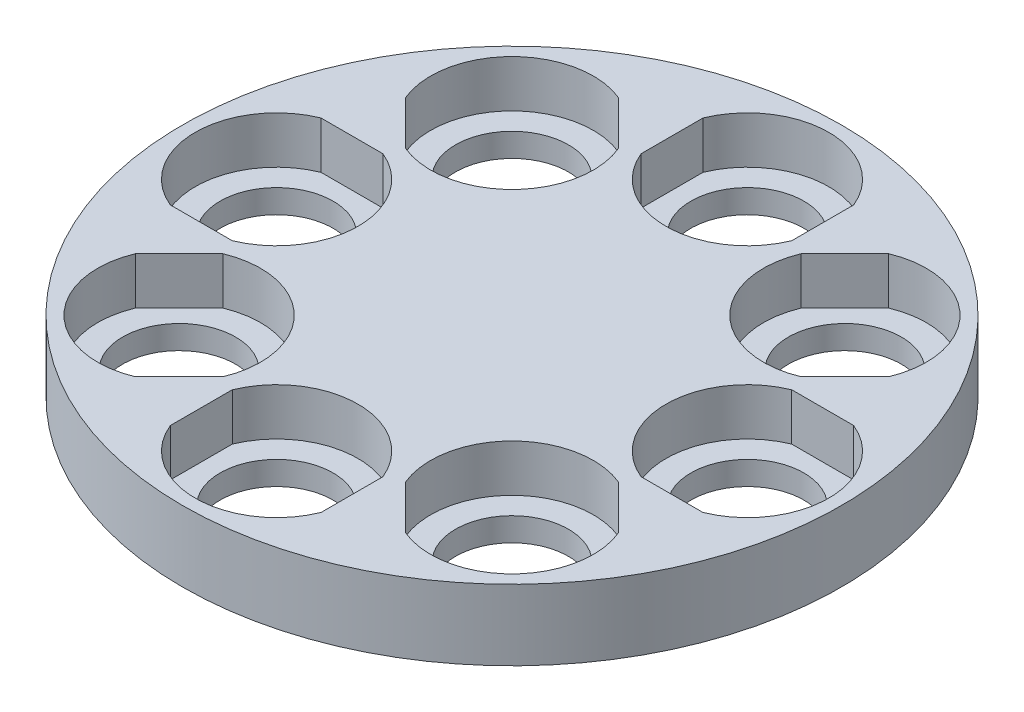
SolidWorks part; units mm, degrees
ref_plane "Front Plane" through (0, 0, 0) normal (0, 0, 1) x (1, 0, 0)
ref_plane "Top Plane" through (0, 0, 0) normal (0, 1, 0) x (1, 0, 0)
ref_plane "Right Plane" through (0, 0, 0) normal (1, 0, 0) x (0, 0, -1)
sketch "Sketch1" plane through (0, 0, 0) normal (0, 1, 0) x (1, 0, 0)
  line L0 (70, 0) -> (50, 0) construction
  circle A0 centre (0, 0) radius 70
  circle A1 centre (50, 0) radius 12
  circle A2 centre (35.3553, -35.3553) radius 12
  circle A3 centre (0, -50) radius 12
  circle A4 centre (-35.3553, -35.3553) radius 12
  circle A5 centre (-50, 0) radius 12
  circle A6 centre (-35.3553, 35.3553) radius 12
  circle A7 centre (0, 50) radius 12
  circle A8 centre (35.3553, 35.3553) radius 12
  point P23 (0, 0)
  dimension "D1" = 140
  dimension "D3" = 24
  dimension "D2" = 20
  dimension "D4" = 8
extrude "Boss-Extrude1" add sketch "Sketch1" along normal blind 25
sketch "Sketch2" plane through (0, 25, 0) normal (0, 1, 0) x (1, 0, 0)
  line L0 (50, 0) -> (50, 16) construction
  line L1 (50, 16) -> (43.4205, 16)
  line L2 (50, 16) -> (56.5795, 16)
  line L3 (32.7, 0) -> (67.3, 0) construction
  line L4 (50, -16) -> (56.5795, -16)
  line L5 (50, -16) -> (43.4205, -16)
  line L6 (46.669, -24.0416) -> (42.0166, -19.3892)
  line L7 (24.0416, -46.669) -> (19.3892, -42.0166)
  line L8 (24.0416, -46.669) -> (28.694, -51.3215)
  line L9 (46.669, -24.0416) -> (51.3215, -28.694)
  line L10 (16, -50) -> (16, -43.4205)
  line L11 (-16, -50) -> (-16, -43.4205)
  line L12 (-16, -50) -> (-16, -56.5795)
  line L13 (16, -50) -> (16, -56.5795)
  line L14 (-24.0416, -46.669) -> (-19.3892, -42.0166)
  line L15 (-46.669, -24.0416) -> (-42.0166, -19.3892)
  line L16 (-46.669, -24.0416) -> (-51.3215, -28.694)
  line L17 (-24.0416, -46.669) -> (-28.694, -51.3215)
  line L18 (-50, -16) -> (-43.4205, -16)
  line L19 (-50, 16) -> (-43.4205, 16)
  line L20 (-50, 16) -> (-56.5795, 16)
  line L21 (-50, -16) -> (-56.5795, -16)
  line L22 (-46.669, 24.0416) -> (-42.0166, 19.3892)
  line L23 (-24.0416, 46.669) -> (-19.3892, 42.0166)
  line L24 (-24.0416, 46.669) -> (-28.694, 51.3215)
  line L25 (-46.669, 24.0416) -> (-51.3215, 28.694)
  line L26 (-16, 50) -> (-16, 43.4205)
  line L27 (16, 50) -> (16, 43.4205)
  line L28 (16, 50) -> (16, 56.5795)
  line L29 (-16, 50) -> (-16, 56.5795)
  line L30 (24.0416, 46.669) -> (19.3892, 42.0166)
  line L31 (46.669, 24.0416) -> (42.0166, 19.3892)
  line L32 (46.669, 24.0416) -> (51.3215, 28.694)
  line L33 (24.0416, 46.669) -> (28.694, 51.3215)
  arc A0 (43.4205, 16) -> (43.4205, -16) centre (50, 0) ccw
  arc A1 (56.5795, -16) -> (56.5795, 16) centre (50, 0) ccw
  arc A2 (42.0166, -19.3892) -> (19.3892, -42.0166) centre (35.3553, -35.3553) ccw
  arc A3 (28.694, -51.3215) -> (51.3215, -28.694) centre (35.3553, -35.3553) ccw
  arc A4 (16, -43.4205) -> (-16, -43.4205) centre (0, -50) ccw
  arc A5 (-16, -56.5795) -> (16, -56.5795) centre (0, -50) ccw
  arc A6 (-19.3892, -42.0166) -> (-42.0166, -19.3892) centre (-35.3553, -35.3553) ccw
  arc A7 (-51.3215, -28.694) -> (-28.694, -51.3215) centre (-35.3553, -35.3553) ccw
  arc A8 (-43.4205, -16) -> (-43.4205, 16) centre (-50, 0) ccw
  arc A9 (-56.5795, 16) -> (-56.5795, -16) centre (-50, 0) ccw
  arc A10 (-42.0166, 19.3892) -> (-19.3892, 42.0166) centre (-35.3553, 35.3553) ccw
  arc A11 (-28.694, 51.3215) -> (-51.3215, 28.694) centre (-35.3553, 35.3553) ccw
  arc A12 (-16, 43.4205) -> (16, 43.4205) centre (0, 50) ccw
  arc A13 (16, 56.5795) -> (-16, 56.5795) centre (0, 50) ccw
  arc A14 (19.3892, 42.0166) -> (42.0166, 19.3892) centre (35.3553, 35.3553) ccw
  arc A15 (51.3215, 28.694) -> (28.694, 51.3215) centre (35.3553, 35.3553) ccw
  point P61 (0, 0)
  dimension "D1" = 34.6
  dimension "D2" = 16
  dimension "D3" = 8
extrude "Cut-Extrude1" cut sketch "Sketch2" against normal blind 10
ref_plane "Plane1" through (0, 10, 0) normal (0, 1, 0) x (1, 0, 0)
split "Split1" trim tools "Plane1" bodies to split 102 resulting bodies 103 104
delete or keep bodies "Body-Delete/Keep 1" type delete bodies bodies 104
sketch "Sketch3" plane through (0, 10, 0) normal (0, -1, 0) x (1, 0, 0)
  circle A0 centre (0, 0) radius 20
  dimension "D1" = 40
extrude "Cut-Extrude2" cut sketch "Sketch3" against normal blind 7.5
